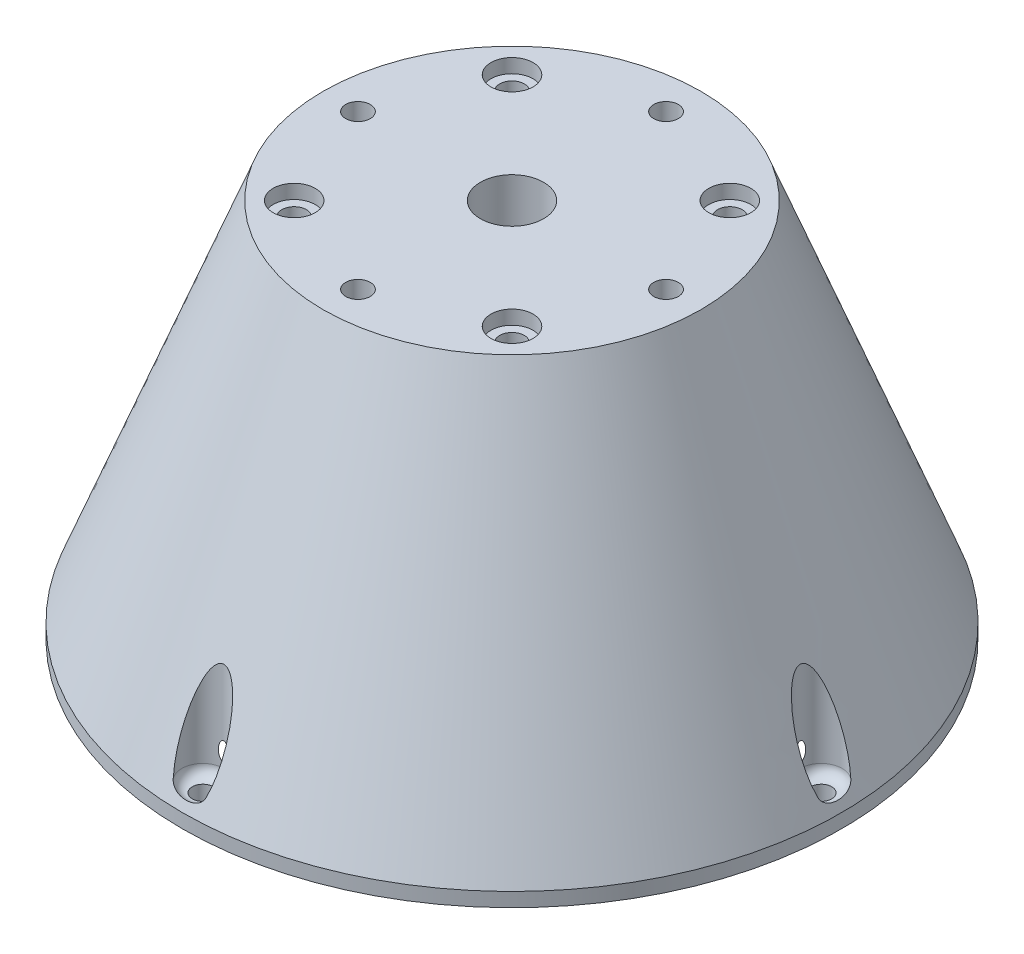
SolidWorks part; units mm, degrees
material "自定义塑料"
ref_plane "前视基准面" through (0, 0, 0) normal (0, 0, 1) x (1, 0, 0)
ref_plane "上视基准面" through (0, 0, 0) normal (0, 1, 0) x (1, 0, 0)
ref_plane "右视基准面" through (0, 0, 0) normal (1, 0, 0) x (0, 0, -1)
sketch "草图1" plane through (0, 0, 0) normal (0, 0, 1) x (1, 0, 0)
  line L0 (0, 0) -> (26.9, 0)
  line L6 (43.5538, -52) -> (46.9, -52)
  line L7 (46.9, -52) -> (26.9, 0)
  line L9 (0, 0) -> (0, -12.6)
  line L10 (0, -12.6) -> (26.9, -12.6)
  line L14 (26.9, -12.6) -> (28.4, -12.6)
  line L15 (28.4, -12.6) -> (43.5538, -52)
revolve "旋转1" add sketch "草图1" angle 360 about L9
sketch "草图2" plane through (0, 0, 0) normal (0, 1, 0) x (1, 0, 0)
  line L1 (-15.5, 15.5) -> (15.5, 15.5)
  line L2 (-15.5, 15.5) -> (-15.5, -15.5)
  line L3 (-15.5, -15.5) -> (15.5, -15.5)
  line L4 (15.5, 15.5) -> (15.5, -15.5)
  line L5 (-15.5, 15.5) -> (15.5, -15.5) construction
  line L6 (-15.5, -15.5) -> (15.5, 15.5) construction
  circle A0 centre (15.5, 15.5) radius 1.75
  circle A1 centre (15.5, -15.5) radius 1.75
  circle A2 centre (-15.5, -15.5) radius 1.75
  circle A3 centre (-15.5, 15.5) radius 1.75
  circle A4 centre (0, 21.9203) radius 1.75
  circle A5 centre (15.5, 15.5) radius 1.75
  circle A6 centre (21.9203, 0) radius 1.75
  circle A7 centre (15.5, -15.5) radius 1.75
  circle A8 centre (0, -21.9203) radius 1.75
  circle A9 centre (-15.5, -15.5) radius 1.75
  circle A10 centre (-21.9203, 0) radius 1.75
  point P0 (0, 0)
  point P16 (0, 0)
  point P30 (0, 0)
  dimension "D1" = 4
  dimension "D2" = 8
extrude "切除-拉伸1" cut sketch "草图2" against normal through all contours L1 A3 L2 | L2 A3 L1 | L4 A0 L1 | L1 A0 L4 | L3 A1 L4 | L4 A1 L3 | L2 A2 L3 | L3 A2 L2 | A4 | A10 | A6 | A8 region at (-15.7476, 0, -15.7476) region at (-14.7573, 0, -14.7573) region at (15.7476, 0, -15.7476) region at (14.7573, 0, -14.7573) region at (-14.7573, 0, 14.7573) region at (-15.7476, 0, 15.7476) region at (15.7476, 0, 15.7476) region at (14.7573, 0, 14.7573) region at (0, 0, -21.9203) region at (21.9203, 0, 0) region at (-21.9203, 0, 0)
sketch "草图3" plane through (0, -12.6, 0) normal (0, -1, 0) x (1, 0, 0)
  line L0 (0, -21.9203) -> (-21.9203, 0)
  line L1 (15.5, -15.5) -> (-15.5, -15.5)
  line L2 (15.5, -15.5) -> (15.5, 15.5)
  line L3 (15.5, 15.5) -> (-15.5, 15.5)
  line L4 (-15.5, -15.5) -> (-15.5, 15.5)
  line L5 (15.5, -15.5) -> (-15.5, 15.5) construction
  line L6 (15.5, 15.5) -> (-15.5, -15.5) construction
  line L7 (-15.5, -15.5) -> (-15.5, 15.5)
  line L8 (-21.9203, 0) -> (0, 21.9203)
  line L9 (-15.5, 15.5) -> (15.5, 15.5)
  line L10 (0, 21.9203) -> (21.9203, 0)
  line L11 (15.5, 15.5) -> (15.5, -15.5)
  line L12 (21.9203, 0) -> (0, -21.9203)
  line L13 (-21.9203, 3.2909) -> (-24.7703, 1.6454)
  line L14 (-3.2909, -21.9203) -> (-1.6454, -24.7703)
  line L15 (-1.6454, -24.7703) -> (1.6454, -24.7703)
  line L16 (1.6454, -24.7703) -> (3.2909, -21.9203)
  line L17 (3.2909, -21.9203) -> (1.6454, -19.0703)
  line L18 (1.6454, -19.0703) -> (-1.6454, -19.0703)
  line L19 (-1.6454, -19.0703) -> (-3.2909, -21.9203)
  line L20 (-24.7703, 1.6454) -> (-24.7703, -1.6454)
  line L21 (-24.7703, -1.6454) -> (-21.9203, -3.2909)
  line L22 (-21.9203, -3.2909) -> (-19.0703, -1.6454)
  line L23 (-19.0703, -1.6454) -> (-19.0703, 1.6454)
  line L24 (-19.0703, 1.6454) -> (-21.9203, 3.2909)
  line L25 (3.2909, 21.9203) -> (1.6454, 24.7703)
  line L26 (1.6454, 24.7703) -> (-1.6454, 24.7703)
  line L27 (-1.6454, 24.7703) -> (-3.2909, 21.9203)
  line L28 (-3.2909, 21.9203) -> (-1.6454, 19.0703)
  line L29 (-1.6454, 19.0703) -> (1.6454, 19.0703)
  line L30 (1.6454, 19.0703) -> (3.2909, 21.9203)
  line L31 (21.9203, -3.2909) -> (24.7703, -1.6454)
  line L32 (24.7703, -1.6454) -> (24.7703, 1.6454)
  line L33 (24.7703, 1.6454) -> (21.9203, 3.2909)
  line L34 (21.9203, 3.2909) -> (19.0703, 1.6454)
  line L35 (19.0703, 1.6454) -> (19.0703, -1.6454)
  line L36 (19.0703, -1.6454) -> (21.9203, -3.2909)
  circle A0 centre (0, -21.9203) radius 2.85 construction
  circle A1 centre (-21.9203, 0) radius 2.85 construction
  circle A2 centre (0, 21.9203) radius 2.85 construction
  circle A3 centre (21.9203, 0) radius 2.85 construction
  point P0 (0, 0)
  point P24 (0, 0)
  point P50 (0, 0)
  dimension "D2" = 5.7
  dimension "D1" = 8
  dimension "D3" = 4
extrude "切除-拉伸2" cut sketch "草图3" against normal blind 8 contours L0 L19 L14 L15 L16 L17 L12 | L18 L19 L0 L12 L17 | L12 L36 L31 L32 L33 L34 L10 | L35 L36 L12 L10 L34 | L10 L30 L25 L26 L27 L28 L8 | L29 L30 L10 L8 L28 | L8 L24 L13 L20 L21 L22 L0 | L23 L24 L8 L0 L22 region at (0, -12.6, -22.5435) region at (0, -12.6, -20.1091) region at (-22.5435, -12.6, 0) region at (-20.1091, -12.6, 0) region at (20.1091, -12.6, 0) region at (22.5435, -12.6, 0) region at (0, -12.6, 22.5435) region at (0, -12.6, 20.1091)
sketch "草图4" plane through (0, 0, 0) normal (0, 1, 0) x (1, 0, 0)
  circle A0 centre (-15.5, -15.5) radius 3
  circle A1 centre (-15.5, 15.5) radius 3
  circle A2 centre (15.5, 15.5) radius 3
  circle A3 centre (15.5, -15.5) radius 3
  point P12 (0, 0)
  dimension "D1" = 4
extrude "切除-拉伸3" cut sketch "草图4" against normal blind 2
sketch "草图5" plane through (0, -12.6, 0) normal (0, -1, 0) x (1, 0, 0)
  circle A0 centre (0, 0) radius 11.1
extrude "切除-拉伸4" cut sketch "草图5" against normal blind 2.2
sketch "草图6" plane through (0, -10.4, 0) normal (0, -1, 0) x (1, 0, 0)
  circle A0 centre (0, 0) radius 4.5
extrude "切除-拉伸5" cut sketch "草图6" against normal through all
sketch "草图7" plane through (0, -52, 0) normal (0, -1, 0) x (1, 0, 0)
  circle A0 centre (0, 0) radius 46.9
  circle A1 centre (0, 0) radius 40
extrude "凸台-拉伸1" add sketch "草图7" along normal blind 2
fillet "圆角1" radius 10 1 edges at (0, -52, 43.5538)
sketch "草图9" plane through (0, 0, 0) normal (0, 1, 0) x (1, 0, 0)
  line L0 (0, 0) -> (0, -44)
  circle A0 centre (0, -44) radius 3
  circle A1 centre (-44, 0) radius 3
  circle A2 centre (0, 44) radius 3
  circle A3 centre (44, 0) radius 3
  point P13 (0, 0)
  dimension "D2" = 4
  dimension "D1" = 44
extrude "切除-拉伸6" cut sketch "草图9" against normal blind 51 contours A0 | A3 | A1 | A2 region at (-2.0613, 0, 46.0613) region at (-44, 0, 0) region at (0, 0, -44) region at (44, 0, 0)
sketch "草图10" plane through (0, -51, 0) normal (0, 1, 0) x (1, 0, 0)
  circle A0 centre (0, -44) radius 1.5
  circle A1 centre (-44, 0) radius 1.5
  circle A2 centre (0, 44) radius 1.5
  circle A3 centre (44, 0) radius 1.5
  point P12 (0, 0)
  dimension "D1" = 4
extrude "切除-拉伸7" cut sketch "草图10" against normal through all
fillet "圆角2" radius 1.5 4 edges at (-41, -51, 0) (0, -51, -41) (41, -51, 0) (0, -51, 41)
